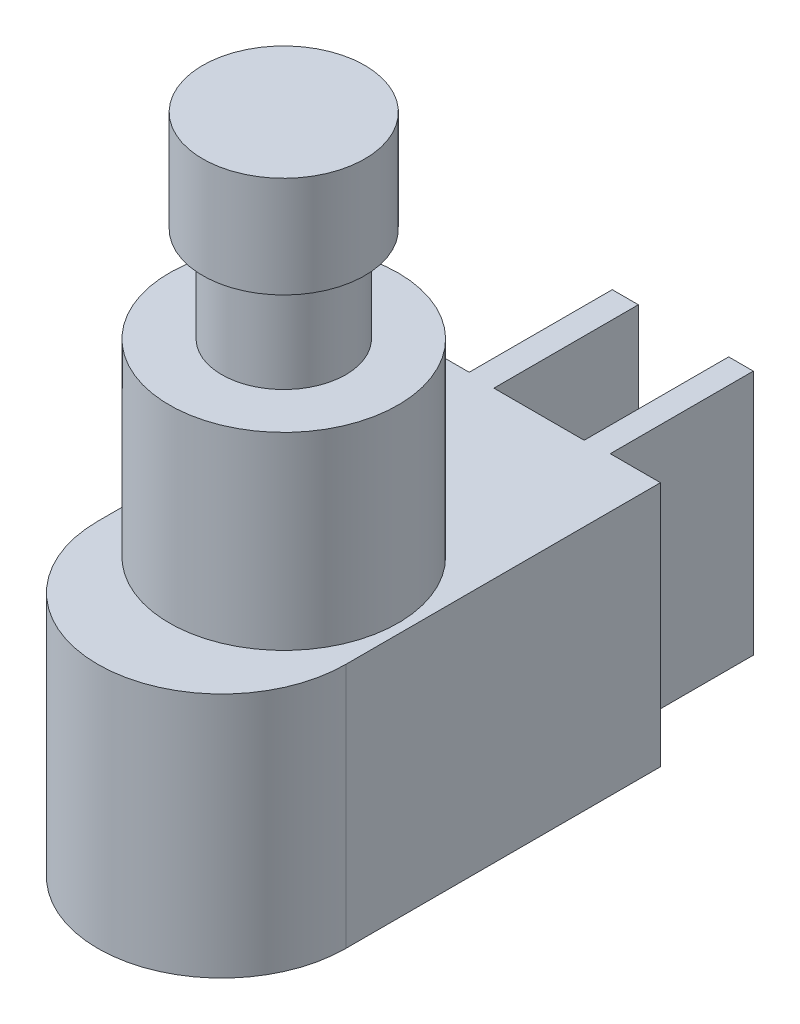
SolidWorks part; units mm, degrees
ref_plane "前视基准面" through (0, 0, 0) normal (0, 0, 1) x (1, 0, 0)
ref_plane "上视基准面" through (0, 0, 0) normal (0, 1, 0) x (1, 0, 0)
ref_plane "右视基准面" through (0, 0, 0) normal (1, 0, 0) x (0, 0, -1)
sketch "草图1" plane through (0, 0, 0) normal (0, 1, 0) x (1, 0, 0)
  circle A0 centre (0, 0) radius 6
  dimension "D1" = 12
extrude "凸台-拉伸1" add sketch "草图1" along normal blind 9.9
sketch "草图2" plane through (0, 9.9, 0) normal (0, 1, 0) x (1, 0, 0)
  circle A0 centre (0, 0) radius 4.25
  dimension "D1" = 8.5
extrude "凸台-拉伸2" add sketch "草图2" along normal blind 10.3
extrude "切除-拉伸-薄壁1" cut sketch "草图2<2>" along normal blind 5 thin thin type one direction reverse wall 1
sketch "草图2<2>" plane through (0, 9.9, 0) normal (0, 1, 0) x (1, 0, 0) same geometry as "草图2"
sketch "草图3" plane through (0, 0, 0) normal (0, -1, 0) x (1, 0, 0)
  line L1 (6.5, 3.25) -> (-6.5, 3.25)
  line L2 (6.5, 3.25) -> (6.5, -13.25)
  line L3 (6.5, -13.25) -> (-6.5, -13.25)
  line L4 (-6.5, 3.25) -> (-6.5, -13.25)
  line L5 (3.8682, -13.25) -> (-3.528, -13.25)
  line L6 (3.8682, -13.25) -> (3.8682, -20.75)
  line L7 (3.8682, -20.75) -> (-3.528, -20.75)
  line L8 (-3.528, -13.25) -> (-3.528, -20.75)
  circle A0 centre (0, 3.25) radius 6.5
  circle A3 centre (0, 0) radius 3.25 construction
  point P4 (0, 3.25)
  point P12 (0, -13.25)
  circle M7 centre (0, 0) radius 6
  dimension "D3" = 13
  dimension "D1" = 16.5
  dimension "D2" = 13
  dimension "D4" = 7.5
extrude "凸台-拉伸3" add sketch "草图3" along normal blind 12.9 contours L1 A0 M7 | L1 M7 | A0 L1 M7 | A0 M7 | A0 L1 M7 | L1 A0 M7 | A0 L4 L3 L2 M7 | L3 L8 L7 L6 region at (5.9377, 0, 2.3954) region at (0, 0, 6.6909) region at (0, 0, -8.4895) region at (0, 0, 0.3801) region at (0, 0, 4.3749) region at (-5.9377, 0, 2.3954) region at (0, 0, -3.5459) region at (0.1701, 0, -17)
sketch "草图4" plane through (0, 0, 0) normal (0, 1, 0) x (1, 0, 0)
  line L0 (3.8682, 20.75) -> (-3.528, 20.75) construction
  line L1 (2.575, 13.175) -> (-2.1589, 13.175)
  line L2 (2.575, 13.175) -> (2.575, 20.75)
  line L3 (2.575, 20.75) -> (-2.1589, 20.75)
  line L4 (-2.1589, 13.175) -> (-2.1589, 20.75)
extrude "切除-拉伸1" cut sketch "草图4" against normal blind 12.9
